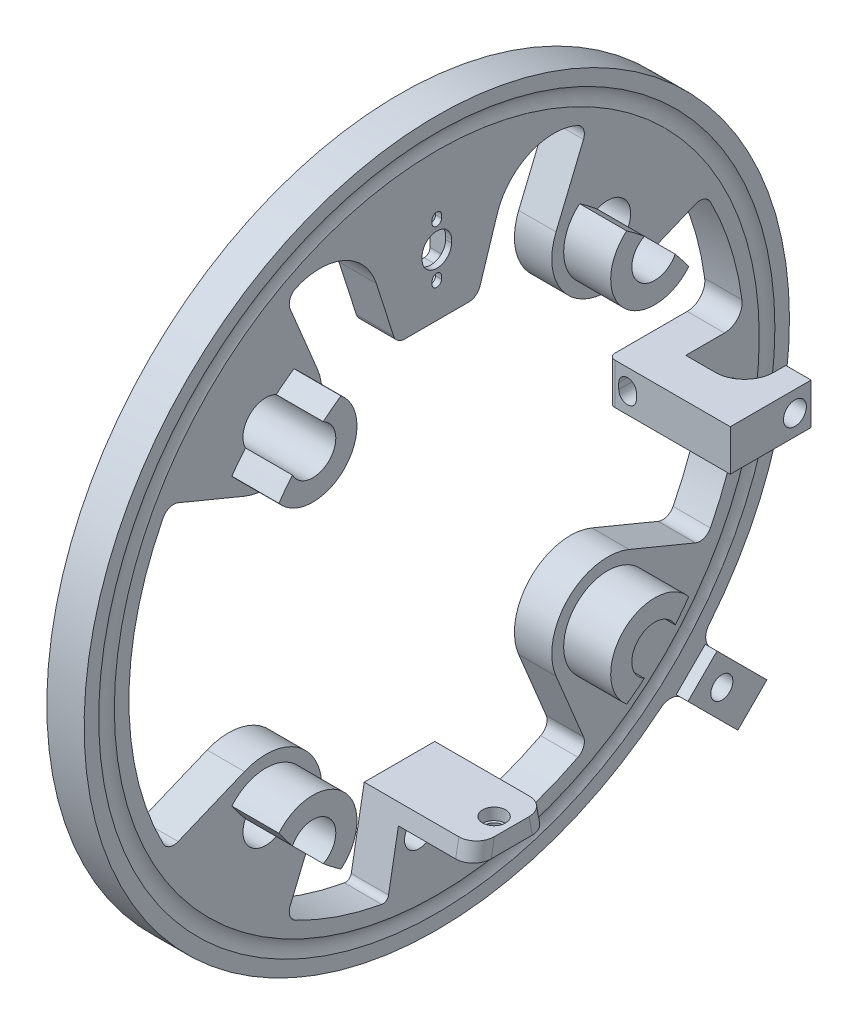
SolidWorks part; units mm, degrees
ref_plane "Front Plane" through (0, 0, 0) normal (0, 0, 1) x (1, 0, 0)
ref_plane "Top Plane" through (0, 0, 0) normal (0, 1, 0) x (1, 0, 0)
ref_plane "Right Plane" through (0, 0, 0) normal (1, 0, 0) x (0, 0, -1)
sketch "Sketch8" plane through (0, 0, 0) normal (1, 0, 0) x (0, 0, -1)
  line L1 (60, 60) -> (-60, 60) construction
  line L2 (60, 60) -> (60, -60) construction
  line L3 (60, -60) -> (-60, -60) construction
  line L4 (-60, 60) -> (-60, -60) construction
  line L5 (60, 60) -> (-60, -60) construction
  line L6 (60, -60) -> (-60, 60) construction
  point P0 (0, 0)
  dimension "D1" = 120
sketch "Sketch1" plane through (0, 0, 0) normal (1, 0, 0) x (0, 0, -1)
  line L0 (-60, 0) -> (-56.19, 0) construction
  line L1 (-56.19, 0) -> (-52.38, 0) construction
  circle A0 centre (0, 0) radius 56.19 construction
  circle A1 centre (0, 0) radius 60
  circle A2 centre (0, 0) radius 52.38
  dimension "D1" = 112.38
  dimension "D2" = 120
extrude "Boss-Extrude1" add sketch "Sketch1" along normal blind 6.35
sketch "Sketch2" plane through (0, 0, 0) normal (-1, 0, 0) x (0, 0, 1)
  line L0 (-20.2833, 32.7284) -> (-28.5792, 52.7563)
  line L1 (-60, -60) -> (60, -60) construction
  line L2 (-60, -60) -> (-60, 60) construction
  line L3 (-60, 60) -> (60, 60) construction
  line L4 (60, -60) -> (60, 60) construction
  line L5 (-60, -60) -> (60, 60) construction
  line L6 (-60, 60) -> (60, -60) construction
  line L7 (-28.5792, 52.7563) -> (-52.7563, 28.5792)
  line L8 (-52.7563, 28.5792) -> (-32.7284, 20.2833)
  circle A0 centre (0, 0) radius 52.38 construction
  arc A1 (-32.7284, 20.2833) -> (-20.2833, 32.7284) centre (-29.0833, 29.0833) ccw
  circle A3 centre (0, 0) radius 60 construction
  circle A5 centre (-29.0833, 29.0833) radius 11.25 construction
  circle A6 centre (0, 0) radius 52.78 construction
  point P0 (0, 0)
  point P10 (-40.6678, 40.6678)
  dimension "D2" = 19.05
  dimension "D3" = 45
  dimension "D5" = 105.56
  dimension "D4" = 22.5
  dimension "D1" = 120
extrude "Boss-Extrude2" add sketch "Sketch2" against normal up to surface (6.35 mm away) up to face at (6.35, 0, -60)
sketch "Sketch3" plane through (6.35, 0, 0) normal (1, 0, 0) x (0, 0, -1)
  circle A0 centre (29.0833, 29.0833) radius 7.5
  arc A2 (20.2833, 32.7284) -> (32.7284, 20.2833) centre (29.0833, 29.0833) ccw construction
  dimension "D1" = 15
extrude "Boss-Extrude3" add sketch "Sketch3" along normal blind 8
sketch "Sketch4" plane through (14.35, 0, 0) normal (1, 0, 0) x (0, 0, -1)
  circle A0 centre (29.0833, 29.0833) radius 3.9
  circle A1 centre (29.0833, 29.0833) radius 7.5 construction
  dimension "D1" = 7.8
extrude "Cut-Extrude2" cut sketch "Sketch4" against normal through all contours A0
fillet "Fillet5" radius 2 2 edges at (3.175, 45.6727, -25.6451) (3.175, 25.6451, -45.6727)
ref_axis "Axis1" through (6.35, 0, 0) along (-1, 0, 0)
pattern_circular "CirPattern1" count 4 every 90 about axis through (6.35, 0, 0) along (-1, 0, 0) of "Boss-Extrude3", "Boss-Extrude2", "Cut-Extrude2", "Fillet5"
sketch "Sketch5" plane through (0, 0, 0) normal (-1, 0, 0) x (0, 0, 1)
  line L0 (5.2587, 40) -> (-10.2587, 40) construction
  line L1 (0, 0) -> (0, 60) construction
  line L2 (15.871, 57.8629) -> (-15.871, 57.8629)
  line L3 (15.871, 57.8629) -> (6.9028, 29.8063)
  line L4 (6.9028, 29.8063) -> (-6.9028, 29.8063)
  line L5 (-15.871, 57.8629) -> (-6.9028, 29.8063)
  line L6 (0, 35.5) -> (0, 36) construction
  line L7 (-0.8, 35.5) -> (-0.8, 36)
  line L8 (0.8, 35.5) -> (0.8, 36)
  line L9 (0, 44.5) -> (0, 45) construction
  line L10 (-0.8, 44.5) -> (-0.8, 45)
  line L11 (0.8, 44.5) -> (0.8, 45)
  line L12 (0, 40) -> (0, 40.5) construction
  line L13 (-2.5, 40) -> (-2.5, 40.5)
  line L14 (2.5, 40) -> (2.5, 40.5)
  circle A0 centre (0, 40) radius 2.5
  circle A1 centre (0, 35.5) radius 0.8
  circle A2 centre (0, 44.5) radius 0.8
  circle A3 centre (0, 0) radius 60 construction
  arc A4 (-0.8, 35.5) -> (0.8, 35.5) centre (0, 35.5) ccw
  arc A5 (0.8, 36) -> (-0.8, 36) centre (0, 36) ccw
  arc A6 (-0.8, 44.5) -> (0.8, 44.5) centre (0, 44.5) ccw
  arc A7 (0.8, 45) -> (-0.8, 45) centre (0, 45) ccw
  arc A8 (-2.5, 40) -> (2.5, 40) centre (0, 40) ccw
  arc A9 (2.5, 40.5) -> (-2.5, 40.5) centre (0, 40.5) ccw
  point P14 (0, 35.75)
  point P23 (0, 44.75)
  point P29 (0, 40.25)
  arc M78 (-24.0232, 46.5462) -> (24.0232, 46.5462) centre (0, 0) cw
  dimension "D2" = 9
  dimension "D3" = 5
  dimension "D4" = 1.6
  dimension "D1" = 40
  dimension "D5" = 0.5
extrude "Boss-Extrude5" add sketch "Sketch5" against normal up to surface (6.35 mm away) contours L5 L4 L3 A9 L14 A0 L13 A7 L11 A2 L10 A5 L8 A1 L7 M78 region at (0, 40.3092, 9.8898) up to face at (6.35, 36.5833, 29.0833)
sketch "Sketch6" plane through (0, 0, 0) normal (-1, 0, 0) x (0, 0, 1)
  line L1 (5.2, 33.8) -> (-5.2, 33.8)
  line L2 (5.2, 33.8) -> (5.2, 48.8)
  line L3 (5.2, 48.8) -> (-5.2, 48.8)
  line L4 (-5.2, 33.8) -> (-5.2, 48.8)
  line L5 (5.2, 33.8) -> (-5.2, 48.8) construction
  line L6 (5.2, 48.8) -> (-5.2, 33.8) construction
  arc A1 (-2.5, 40) -> (2.5, 40) centre (0, 40) ccw construction
  point P0 (0, 41.3)
  dimension "D3" = 6.2
  dimension "D1" = 15
  dimension "D2" = 10.4
extrude "Cut-Extrude1" cut sketch "Sketch6" against normal offset from surface (5.35 mm away) 1 up to face at (6.35, 36.5833, 29.0833)
fillet "Fillet1" radius 1 4 edges at (2.675, 33.8, 5.2) (2.675, 48.8, -5.2) (2.675, 48.8, 5.2) (2.675, 33.8, -5.2)
fillet "Fillet2" radius 10.08 2 edges at (3.175, 50.5974, -13.5486) (3.175, 50.5974, 13.5486)
fillet "Fillet3" radius 2 2 edges at (3.175, 29.8063, -6.9028) (3.175, 29.8063, 6.9028)
sketch "Sketch14" plane through (0, 0, 0) normal (-1, 0, 0) x (0, 0, 1)
  line L0 (-59.8978, 0) -> (0, 0) construction
  line L1 (-35.63, 3.5) -> (-59.8978, 3.5)
  line L2 (-35.63, 3.5) -> (-35.63, -3.5)
  line L3 (-35.63, -3.5) -> (-59.8978, -3.5)
  line L4 (-59.8978, 3.5) -> (-59.8978, -3.5)
  line L5 (-35.63, 3.5) -> (-59.8978, -3.5) construction
  line L6 (-35.63, -3.5) -> (-59.8978, 3.5) construction
  circle A0 centre (0, 0) radius 60 construction
  arc A2 (-46.5462, 24.0232) -> (-46.5462, -24.0232) centre (0, 0) ccw construction
  point P0 (-47.7639, 0)
  point P7 (-52.38, 0)
  dimension "D2" = 16.75
  dimension "D1" = 7
extrude "Boss-Extrude8" add sketch "Sketch14" against normal up to surface (6.35 mm away) up to face at (6.35, 36.5833, 29.0833)
fillet "Fillet7" radius 3 2 edges at (3.175, -3.5, -52.2629) (3.175, 3.5, -52.2629)
sketch "Sketch7" plane through (0, 0, 0) normal (0, 1, 0) x (1, 0, 0)
  line L0 (8.636, 56.19) -> (-2.286, 56.19) construction
  line L1 (3.175, 60) -> (3.175, -60) construction
  line L2 (6.35, 60) -> (0, 60) construction
  line L3 (0, -60) -> (6.35, -60) construction
  circle A0 centre (8.636, 56.19) radius 2.645
  circle A1 centre (-2.286, 56.19) radius 2.645
  dimension "D1" = 5.29
  dimension "D2" = 56.19
  dimension "D3" = 10.922
revolve "Cut-Revolve1" cut sketch "Sketch7" angle 360 about axis through (6.35, 0, 0) along (-1, 0, 0)
sketch "Sketch9" plane through (0, 0, 0) normal (-1, 0, 0) x (0, 0, 1)
  line L0 (-54.1628, -49.2131) -> (-49.2131, -54.1628)
  line L1 (-49.2131, -54.1628) -> (-39.8793, -44.829)
  line L2 (-39.8793, -44.829) -> (-44.829, -39.8793)
  line L3 (-44.829, -39.8793) -> (-54.1628, -49.2131)
  line L4 (-60, -60) -> (60, 60) construction
  circle A0 centre (0, 0) radius 60 construction
  point P8 (-51.688, -51.688)
  dimension "D1" = 13.2
  dimension "D2" = 7
extrude "Boss-Extrude6" add sketch "Sketch9" against normal up to surface (6.35 mm away) up to face at (6.35, 0, -60)
fillet "Fillet6" radius 2.54 2 edges at (3.175, -44.829, -39.8793) (3.175, -39.8793, -44.829)
sketch "Sketch10" plane through (6.35, 0, 0) normal (1, 0, 0) x (0, 0, -1)
  line L0 (49.2131, -54.1628) -> (54.1628, -49.2131)
  line L1 (49.2131, -54.1628) -> (40.7278, -45.6776)
  line L2 (54.1628, -49.2131) -> (45.6776, -40.7278)
  line L3 (40.7278, -45.6776) -> (45.6776, -40.7278)
  dimension "D1" = 12
extrude "Boss-Extrude7" add sketch "Sketch10" along normal blind 2
sketch "Sketch15" plane through (6.35, 0, 0) normal (1, 0, 0) x (0, 0, -1)
  line L0 (48.9503, -3.5) -> (35.63, -3.5) construction
  line L1 (35.63, 3.5) -> (49.38, 3.5)
  line L2 (35.63, 3.5) -> (35.63, -3.5)
  line L3 (35.63, -3.5) -> (49.38, -3.5)
  line L4 (49.38, 3.5) -> (49.38, -3.5)
  dimension "D1" = 13.75
extrude "Boss-Extrude9" add sketch "Sketch15" along normal blind 14.3
fillet "Fillet8" radius 1 2 edges at (0, 0, -35.63) (0, -51.688, -51.688)
sketch "Sketch18" plane through (0, 0, 0) normal (0, 0, 1) x (1, 0, 0)
  line L1 (3.175, -0.5) -> (3.175, 0.5) construction
  line L3 (1.675, -0.5) -> (1.675, 0.5)
  line L4 (4.675, -0.5) -> (4.675, 0.5)
  line L5 (0, 0) -> (6.35, 0) construction
  line L6 (0, 60) -> (0, -60) construction
  line L7 (6.35, -60) -> (6.35, 60) construction
  arc A0 (1.675, -0.5) -> (4.675, -0.5) centre (3.175, -0.5) ccw
  arc A1 (4.675, 0.5) -> (1.675, 0.5) centre (3.175, 0.5) ccw
  point P2 (3.175, 0)
  dimension "D1" = 1.5
  dimension "D2" = 1
extrude "Cut-Extrude7" cut sketch "Sketch18" against normal through all
sketch "Sketch19" plane through (0, 0, 0) normal (-1, 0, 0) x (0, 0, 1)
  line L0 (0, -60) -> (0, -32.7201) construction
  line L1 (6, -38.38) -> (-6, -38.38)
  line L2 (6, -38.38) -> (8.5, -52.38)
  line L3 (8.5, -52.38) -> (-8.5, -52.38)
  line L4 (-6, -38.38) -> (-8.5, -52.38)
  line L5 (-60, -60) -> (60, -60) construction
  arc A0 (-24.0232, -46.5462) -> (24.0232, -46.5462) centre (0, 0) ccw construction
  circle A1 centre (3, -44) radius 2.5
  circle A2 centre (-3, -44) radius 2.5
  dimension "D1" = 5
  dimension "D2" = 16
  dimension "D5" = 6
  dimension "D3" = 12
  dimension "D4" = 17
  dimension "D6" = 5.62
extrude "Boss-Extrude10" add sketch "Sketch19" against normal up to surface (6.35 mm away) up to face at (6.35, 35.75, 0)
fillet "Fillet9" radius 1 2 edges at (3.175, -51.7054, -8.3795) (3.175, -51.7054, 8.3795)
sketch "Sketch20" plane through (14.35, 0, 0) normal (1, 0, 0) x (0, 0, -1)
  circle A0 centre (0, 0) radius 42.5
  circle A1 centre (0, 0) radius 60
  arc A2 (46.3255, -38.1306) -> (38.1306, -46.3255) centre (0, 0) ccw construction
  dimension "D1" = 85
extrude "Cut-Extrude8" cut sketch "Sketch20" against normal up to surface (8 mm away) and the other way blind 4 up to face at (6.35, -1.7736, -7.0879)
sketch "Sketch23" plane through (6.35, 0, 0) normal (1, 0, 0) x (0, 0, -1)
  line L0 (6, -38.38) -> (-6, -38.38)
  line L1 (-6, -38.38) -> (-6.5357, -41.38)
  line L2 (-8.2049, -50.7274) -> (-6, -38.38) construction
  line L3 (-6.5357, -41.38) -> (6.5357, -41.38)
  line L4 (6, -38.38) -> (8.2049, -50.7274) construction
  line L5 (6.5357, -41.38) -> (6, -38.38)
  dimension "D1" = 3
extrude "Boss-Extrude11" add sketch "Sketch23" along normal blind 12.75
fillet "Fillet11" radius 3 2 edges at (19.1, -39.88, -6.2679) (19.1, -39.88, 6.2679)
sketch "Sketch24" plane through (0, -38.38, 0) normal (0, 1, 0) x (1, 0, 0)
  line L0 (16.1, 0) -> (0, 0) construction
  line L1 (0, -6) -> (0, 6) construction
  circle A0 centre (16.1, 0) radius 1.95
  dimension "D1" = 3.9
  dimension "D2" = 9.75
extrude "Cut-Extrude9" cut sketch "Sketch24" against normal offset from surface (2 mm away) 1 up to face at (14.0571, -41.38, 0)
sketch "Sketch25" plane through (0, -40.38, 0) normal (0, 1, 0) x (1, 0, 0)
  circle A0 centre (16.1, 0) radius 1.5
  dimension "D1" = 3
extrude "Cut-Extrude10" cut sketch "Sketch25" against normal up to surface (1 mm away) up to face at (14.0571, -41.38, 0)
sketch "Sketch26" plane through (8.35, 0, 0) normal (1, 0, 0) x (0, 0, -1)
  line L0 (60, -60) -> (-60, 60) construction
  circle A0 centre (46.4993, -46.4993) radius 1.875
  dimension "D1" = 3.75
  dimension "D2" = 65.76
extrude "Cut-Extrude11" cut sketch "Sketch26" against normal offset from surface (6.35 mm away) 2 up to face at (0, -31.528, -31.528)
sketch "Sketch29" plane through (0, -3.5, 0) normal (0, -1, 0) x (1, 0, 0)
  line L0 (20.65, -49.38) -> (18.35, -49.38) construction
  line L1 (18.35, -42.3556) -> (16.35, -42.3556)
  line L2 (18.35, -42.3556) -> (18.35, -49.38)
  line L3 (18.35, -49.38) -> (16.35, -49.38)
  line L4 (16.35, -42.3556) -> (16.35, -49.38)
  dimension "D1" = 2
extrude "Boss-Extrude12" add sketch "Sketch29" against normal up to surface (7 mm away) up to face at (10.1659, 3.5, -43.2283)
sketch "Sketch27" plane through (20.65, 0, 0) normal (1, 0, 0) x (0, 0, -1)
  circle A0 centre (46.63, 0) radius 1.95
  dimension "D1" = 3.9
  dimension "D2" = 46.63
extrude "Cut-Extrude13" cut sketch "Sketch27" against normal up to surface (4.3 mm away) up to face at (16.35, 0, -45.9039)
fillet "Fillet12" radius 5 1 edges at (16.35, 0, -42.5)
fillet "Fillet13" radius 0.5 8 edges at (5.35, 34.0929, -4.9071) (5.35, 41.3, -5.2) (5.35, 48.5071, -4.9071) (5.35, 48.8, 0) (5.35, 48.5071, 4.9071) (5.35, 41.3, 5.2) (5.35, 34.0929, 4.9071) (5.35, 33.8, 0)
